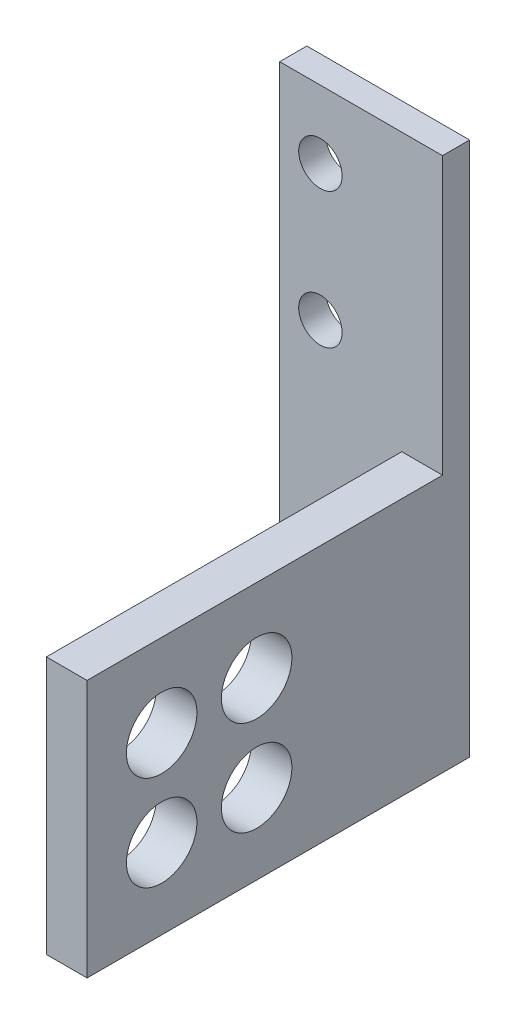
SolidWorks part; units mm, degrees
ref_plane "Front Plane" through (0, 0, 0) normal (0, 0, 1) x (1, 0, 0)
ref_plane "Top Plane" through (0, 0, 0) normal (0, 1, 0) x (1, 0, 0)
ref_plane "Right Plane" through (0, 0, 0) normal (1, 0, 0) x (0, 0, -1)
ref_plane "Foot Bottom" through (0, 0, -4) normal (0, 0, 1) x (1, 0, 0)
sketch "Foot Sketch" plane through (0, 0, -4) normal (0, 0, 1) x (1, 0, 0)
  line L0 (-79.35, 54) -> (-67.35, 54)
  line L1 (-67.35, 54) -> (-67.35, 93.4)
  line L2 (-67.35, 93.4) -> (-79.35, 93.4)
  line L3 (-79.35, 93.4) -> (-79.35, 54)
extrude "Foot" add sketch "Foot Sketch" along normal blind 2
ref_axis "Engine Axis" through (-66.75, 0, 0) along (-1, 0, 0)
ref_plane "Upright Base" through (0, 0, -2) normal (0, 0, 1) x (1, 0, 0)
sketch "Upright Sketch" plane through (0, 0, -2) normal (0, 0, 1) x (1, 0, 0)
  line L0 (-70.35, 54) -> (-67.35, 54)
  line L1 (-67.35, 54) -> (-67.35, 73)
  line L2 (-67.35, 73) -> (-70.35, 73)
  line L3 (-70.35, 73) -> (-70.35, 54)
extrude "Upright" add sketch "Upright Sketch" along normal blind 26.2
ref_plane "Hole Plane" through (-70.35, 0, 0) normal (1, 0, 0) x (0, 0, -1)
sketch "Sheath Holes Sketch" plane through (-70.35, 0, 0) normal (1, 0, 0) x (0, 0, -1)
  circle A0 centre (-18.7, 66.9) radius 2.6
  circle A1 centre (-11.7, 59.9) radius 2.6
  circle A2 centre (-11.7, 66.9) radius 2.6
  circle A3 centre (-18.7, 59.9) radius 2.6
extrude "Sheath Holes" cut sketch "Sheath Holes Sketch" along normal blind 3
sketch "Servo Screw Holes Sketch" plane through (0, 0, 0) normal (0, 0, 1) x (1, 0, 0)
  circle A0 centre (-76.35, 78.4) radius 1.6
  circle A1 centre (-76.35, 88.4) radius 1.6
extrude "Servo Screw Holes" cut sketch "Servo Screw Holes Sketch" against normal mid plane 30
